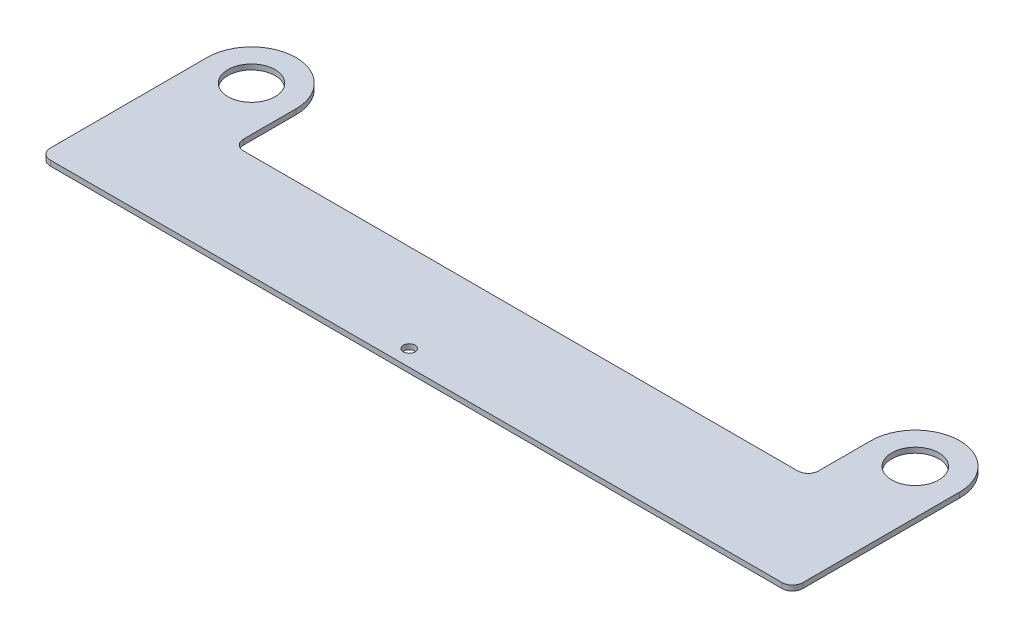
SolidWorks part; units mm, degrees
ref_plane "Front" through (0, 0, 0) normal (0, 0, 1) x (1, 0, 0)
ref_plane "Top" through (0, 0, 0) normal (0, 1, 0) x (1, 0, 0)
ref_plane "Right" through (0, 0, 0) normal (1, 0, 0) x (0, 0, -1)
sketch "Sketch1" plane through (0, 0, 0) normal (0, 1, 0) x (1, 0, 0)
  line L0 (0, 0) -> (403.225, 0) construction
  line L5 (-26.9875, 0) -> (-26.9875, -95.25)
  line L6 (430.2125, 0) -> (430.2125, -95.25)
  line L7 (423.8625, -101.6) -> (-20.6375, -101.6)
  line L8 (26.9875, 0) -> (26.9875, -31.75)
  line L9 (376.2375, 0) -> (376.2375, -31.75)
  line L10 (369.8875, -38.1) -> (33.3375, -38.1)
  circle A0 centre (0, 0) radius 14.2875
  circle A1 centre (403.225, 0) radius 14.2875
  arc A2 (26.9875, 0) -> (-26.9875, 0) centre (0, 0) ccw
  arc A3 (430.2125, 0) -> (376.2375, 0) centre (403.225, 0) ccw
  circle A4 centre (0, 0) radius 26.9875 construction
  circle A5 centre (403.225, 0) radius 26.9875 construction
  arc A6 (376.2375, -31.75) -> (369.8875, -38.1) centre (369.8875, -31.75) cw
  arc A7 (430.2125, -95.25) -> (423.8625, -101.6) centre (423.8625, -95.25) cw
  arc A8 (-26.9875, -95.25) -> (-20.6375, -101.6) centre (-20.6375, -95.25) ccw
  arc A9 (26.9875, -31.75) -> (33.3375, -38.1) centre (33.3375, -31.75) ccw
  point P24 (-26.9875, -101.6)
  point P27 (26.9875, -38.1)
  dimension "D3" = 28.575
  dimension "D5" = 28.575
  dimension "D7" = 6.35
  dimension "D1" = 12.7
  dimension "D2" = 101.6
  dimension "D4" = 403.225
  dimension "D6" = 38.1
extrude "Boss-Extrude1" add sketch "Sketch1" along normal blind 3.175
sketch "Sketch2" plane through (0, 3.175, 0) normal (0, 1, 0) x (1, 0, 0)
  circle A0 centre (187.5091, -91.7077) radius 3.556 construction
  circle A1 centre (187.5091, -91.7077) radius 3.556
extrude "Cut-Extrude1" cut sketch "Sketch2" against normal up to next
